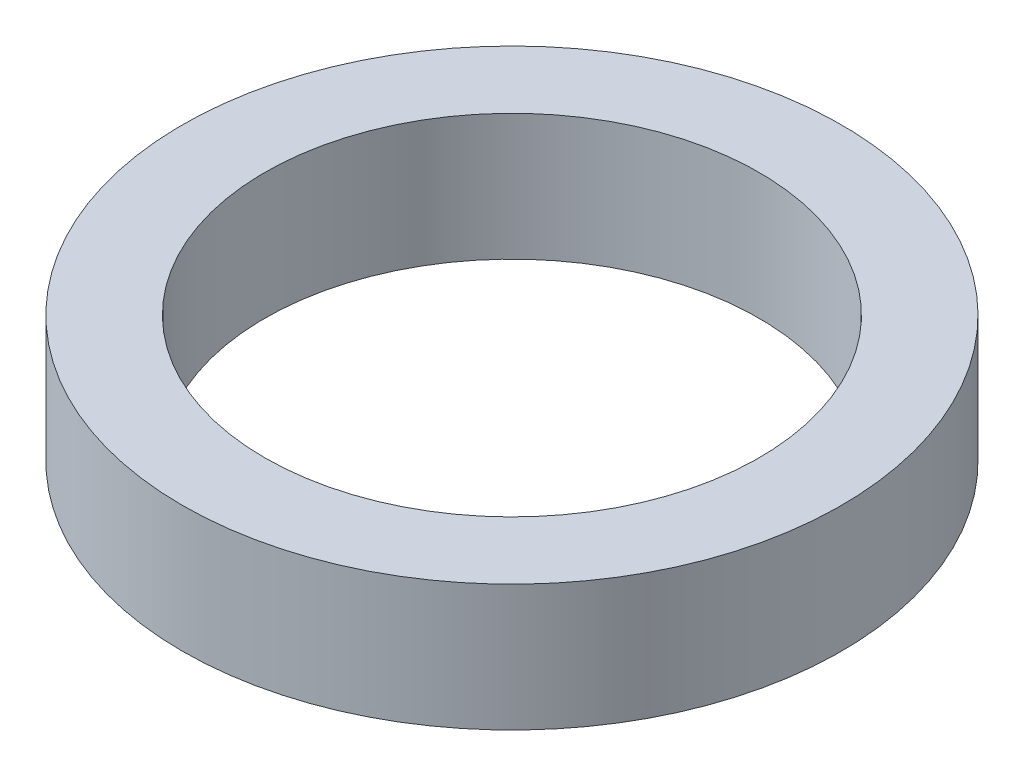
SolidWorks part; units mm, degrees
ref_plane "Front Plane" through (0, 0, 0) normal (0, 0, 1) x (1, 0, 0)
ref_plane "Top Plane" through (0, 0, 0) normal (0, 1, 0) x (1, 0, 0)
ref_plane "Right Plane" through (0, 0, 0) normal (1, 0, 0) x (0, 0, -1)
sketch "Sketch1" plane through (0, 0, 0) normal (0, 1, 0) x (1, 0, 0)
  circle A0 centre (0, 0) radius 60
  dimension "FLANGE_OD" = 120
extrude "Boss-Extrude1" add sketch "Sketch1" along normal blind 23
sketch "Sketch2" plane through (0, 0, 0) normal (0, 1, 0) x (1, 0, 0)
  circle A0 centre (0, 0) radius 45
  dimension "BORE_D" = 90
extrude "Cut-Extrude1" cut sketch "Sketch2" along normal through all
sketch "Sketch3" plane through (0, 23, 0) normal (0, 1, 0) x (1, 0, 0)
  circle A0 centre (0, 0) radius 27.1788 construction
  circle A1 centre (-27.1788, 0) radius 2.3264
  dimension "BOLT_D" = 4.6527
  dimension "BOLT_PCD" = 54.3576
extrude "Cut-Extrude2" cut sketch "Sketch3" against normal blind 20.332 rebuild error yes
pattern_circular "CirPattern1" count 5 over 360 rebuild error yes
